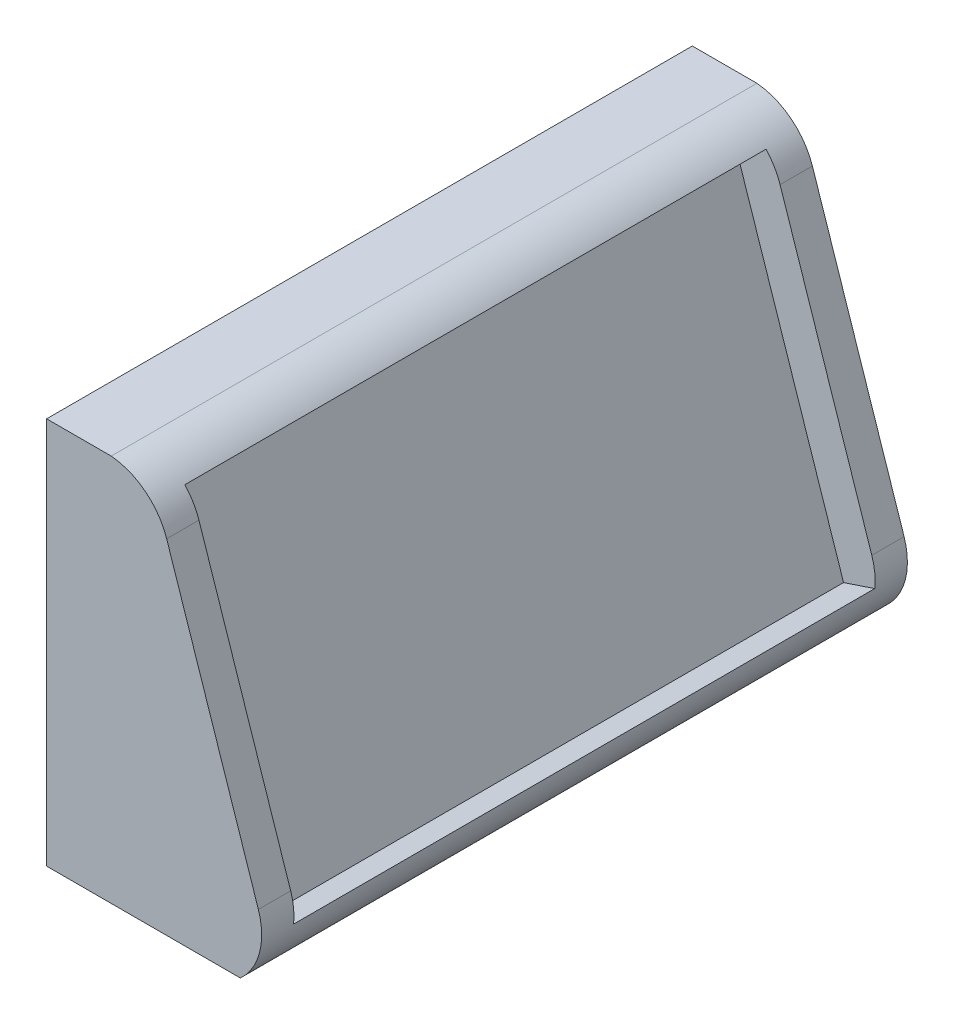
SolidWorks part; units mm, degrees
ref_plane "Front Plane" through (0, 0, 0) normal (0, 0, 1) x (1, 0, 0)
ref_plane "Top Plane" through (0, 0, 0) normal (0, 1, 0) x (1, 0, 0)
ref_plane "Right Plane" through (0, 0, 0) normal (1, 0, 0) x (0, 0, -1)
sketch "Sketch1" plane through (0, 0, 0) normal (1, 0, 0) x (0, 0, -1)
  line L1 (-50, -30) -> (50, -30)
  line L2 (-50, -30) -> (-50, 30)
  line L3 (-50, 30) -> (50, 30)
  line L4 (50, -30) -> (50, 30)
  line L5 (-50, -30) -> (50, 30) construction
  line L6 (-50, 30) -> (50, -30) construction
  point P0 (0, 0)
  dimension "D1" = 60
  dimension "D2" = 100
extrude "Boss-Extrude1" add sketch "Sketch1" along normal blind 10
sketch "Sketch2" plane through (0, 0, 50) normal (0, 0, 1) x (1, 0, 0)
  line L0 (10, 30) -> (30, -30)
  line L1 (30, -30) -> (10, -30)
  line L2 (10, -30) -> (10, 30)
  dimension "D1" = 20
extrude "Boss-Extrude2" add sketch "Sketch2" against normal up to surface (100 mm away) up to face at (5, 0, -50)
sketch "Sketch3" plane through (18, 6, 0) normal (0.9487, 0.3162, 0) x (0, 0, -1)
  line L1 (-50, 25.2982) -> (50, 25.2982)
  line L2 (-50, 25.2982) -> (-50, -37.9473)
  line L3 (-50, -37.9473) -> (50, -37.9473)
  line L4 (50, 25.2982) -> (50, -37.9473)
  line L5 (-45, 20.2982) -> (45, 20.2982)
  line L6 (-45, 20.2982) -> (-45, -32.9473)
  line L7 (-45, -32.9473) -> (45, -32.9473)
  line L8 (45, 20.2982) -> (45, -32.9473)
  dimension "D1" = 5
  dimension "D2" = 5
  dimension "D3" = 5
  dimension "D4" = 5
extrude "Boss-Extrude3" add sketch "Sketch3" along normal blind 6
fillet "Fillet1" radius 10 1 edges at (15.6921, 31.8974, 0)
fillet "Fillet3" radius 10 1 edges at (35.6921, -28.1026, 0)
